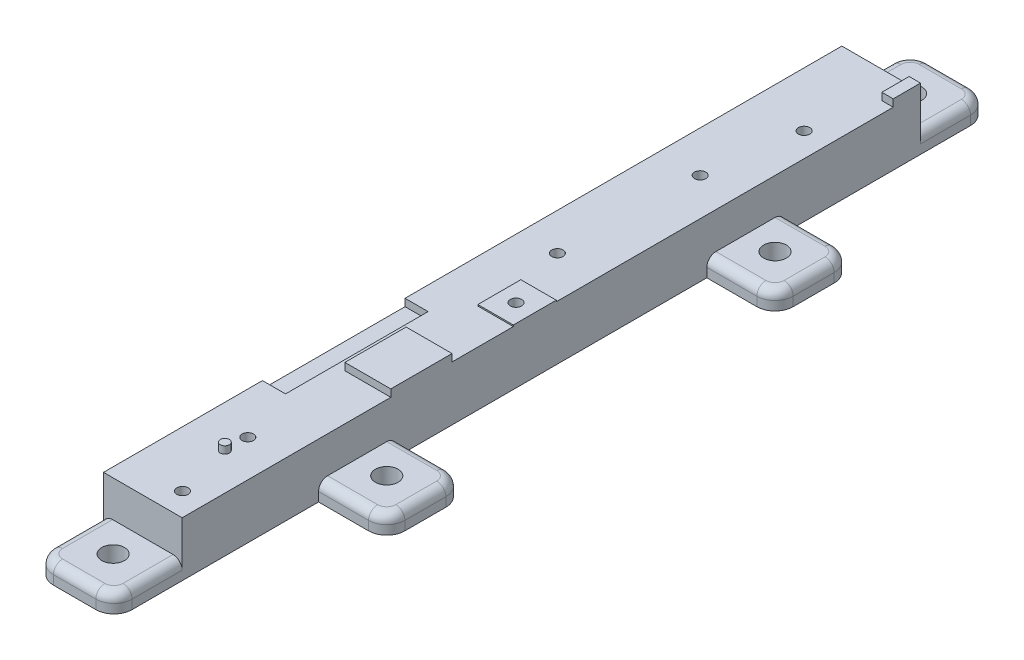
SolidWorks part; units mm, degrees
ref_plane "Front Plane" through (0, 0, 0) normal (0, 0, 1) x (1, 0, 0)
ref_plane "Top Plane" through (0, 0, 0) normal (0, 1, 0) x (1, 0, 0)
ref_plane "Right Plane" through (0, 0, 0) normal (1, 0, 0) x (0, 0, -1)
sketch "Sketch1" plane through (0, 0, 0) normal (0, 1, 0) x (1, 0, 0)
  line L1 (0, 0) -> (-17.3, 0)
  line L2 (0, 0) -> (0, -162.4)
  line L3 (0, -162.4) -> (-17.3, -162.4)
  line L4 (-17.3, 0) -> (-17.3, -162.4)
  line L5 (0, -116.51) -> (-10.1, -116.51)
  line L6 (0, -116.51) -> (0, -103.04)
  line L7 (0, -103.04) -> (-10.1, -103.04)
  line L8 (-10.1, -116.51) -> (-10.1, -103.04)
  line L9 (0, 0) -> (-2.5, 0)
  line L10 (0, 0) -> (0, -6)
  line L11 (0, -6) -> (-2.5, -6)
  line L12 (-2.5, 0) -> (-2.5, -6)
  line L13 (-17.3, -127.44) -> (-12.22, -127.44)
  line L14 (-17.3, -127.44) -> (-17.3, -96.08)
  line L15 (-17.3, -96.08) -> (-12.22, -96.08)
  line L16 (-12.22, -127.44) -> (-12.22, -96.08)
  circle A0 centre (-5.05, -157.28) radius 1.25
  circle A1 centre (-8.115, -144.895) radius 1
  circle A2 centre (-8.115, -139.85) radius 1.25
  circle A3 centre (-3.95, -85.02) radius 1.25
  circle A4 centre (-9.115, -70.745) radius 1.25
  circle A5 centre (-8.25, -40.21) radius 1.25
  circle A6 centre (-5.3, -20.3) radius 1.25
  dimension "D3" = 2.5
  dimension "D6" = 2
  dimension "D9" = 2.5
  dimension "D14" = 2.5
  dimension "D17" = 2.5
  dimension "D20" = 2.5
  dimension "D23" = 2.5
  dimension "D1" = 162.4
  dimension "D2" = 17.3
  dimension "D4" = 5.05
  dimension "D5" = 5.12
  dimension "D7" = 17.505
  dimension "D8" = 8.115
  dimension "D10" = 5.045
  dimension "D11" = 10.1
  dimension "D12" = 13.47
  dimension "D13" = 45.89
  dimension "D15" = 3.95
  dimension "D16" = 77.38
  dimension "D18" = 9.115
  dimension "D19" = 91.655
  dimension "D21" = 8.25
  dimension "D22" = 122.19
  dimension "D24" = 5.3
  dimension "D25" = 142.1
  dimension "D26" = 2.5
  dimension "D27" = 6
  dimension "D28" = 34.96
  dimension "D29" = 66.32
  dimension "D30" = 12.22
extrude "Boss-Extrude1" add sketch "Sketch1" against normal blind 12 contours L16 L13 L4 L3 L2 L5 L8 L7 L11 L12 L1 L15 A6 A5 A4 A3 A2 A1 A0 | L8 L5 L2 L7 | L1 L12 L11 L2 | L13 L16 L15 L4 | A1 region at (-1.25, 0, 3) region at (-8.5237, 0, 77.9924) region at (-5.05, 0, 109.775) region at (-14.76, 0, 111.76) region at (-8.115, 0, 144.895)
extrude "Boss-Extrude2" add sketch "Sketch1<3>" along normal blind 1.6 contours L8 L5 L2 L7 | L1 L12 L11 L2 | A1 region at (-1.25, 0, 3) region at (-5.05, 0, 109.775) region at (-8.115, 0, 144.895)
sketch "Sketch1<3>" plane through (0, 0, 0) normal (0, 1, 0) x (1, 0, 0) same geometry as "Sketch1"
extrude "Cut-Extrude1" cut sketch "Sketch1<4>" against normal blind 1.6 contours L13 L16 L15 L4 region at (-14.76, 0, 111.76)
sketch "Sketch1<4>" plane through (0, 0, 0) normal (0, 1, 0) x (1, 0, 0) same geometry as "Sketch1"
sketch "Sketch2" plane through (0, 0, 0) normal (0, 1, 0) x (1, 0, 0)
  line L0 (0, -6) -> (0, -103.04) construction
  line L1 (0, -80.11) -> (-7.8, -80.11)
  line L2 (0, -80.11) -> (0, -89.56)
  line L3 (0, -89.56) -> (-7.8, -89.56)
  line L4 (-7.8, -80.11) -> (-7.8, -89.56)
  line L5 (0, -162.4) -> (-17.3, -162.4) construction
  line M11 (0, -103.04) -> (0, -6)
  circle M22 centre (-3.95, -85.02) radius 1.25
  dimension "D1" = 72.84
  dimension "D2" = 7.8
  dimension "D3" = 9.45
extrude "Boss-Extrude3" add sketch "Sketch2" along normal blind 0.3 contours L1 L4 L3 M11 M22 region at (-0.1225, 0, 84.835)
sketch "Sketch3" plane through (0, 0, 162.4) normal (0, 0, 1) x (1, 0, 0)
  line L0 (-17.3, -12) -> (-17.3, 0) construction
  line L1 (0, -12) -> (-17.3, -12)
  line L2 (0, -12) -> (0, -8)
  line L3 (0, -8) -> (-17.3, -8)
  line L4 (-17.3, -12) -> (-17.3, -8)
  dimension "D1" = 4
extrude "Boss-Extrude4" add sketch "Sketch3" along normal blind 15
sketch "Sketch4" plane through (0, 0, 0) normal (0, 0, -1) x (-1, 0, 0)
  line L0 (0, -12) -> (0, 1.6) construction
  line L1 (17.3, -12) -> (0, -12)
  line L2 (17.3, -12) -> (17.3, -8)
  line L3 (17.3, -8) -> (0, -8)
  line L4 (0, -12) -> (0, -8)
  dimension "D1" = 4
extrude "Boss-Extrude5" add sketch "Sketch4" along normal blind 15
sketch "Sketch5" plane through (0, 0, 0) normal (1, 0, 0) x (0, 0, -1)
  line L0 (15, -12) -> (-177.4, -12) construction
  line L1 (-132.4, -12) -> (-115.4, -12)
  line L2 (-132.4, -12) -> (-132.4, -8)
  line L3 (-132.4, -8) -> (-115.4, -8)
  line L4 (-115.4, -12) -> (-115.4, -8)
  line L5 (-177.4, -12) -> (-177.4, -8) construction
  line L6 (-47, -12) -> (-30, -12)
  line L7 (-47, -12) -> (-47, -8)
  line L8 (-47, -8) -> (-30, -8)
  line L9 (-30, -12) -> (-30, -8)
  line L10 (15, -8) -> (15, -12) construction
  dimension "D1" = 4
  dimension "D2" = 45
  dimension "D3" = 17
  dimension "D4" = 17
  dimension "D5" = 45
extrude "Boss-Extrude6" add sketch "Sketch5" along normal blind 15
fillet "Fillet1" radius 4 8 edges at (-17.3, -10, -15) (0, -10, -15) (15, -10, 30) (15, -10, 47) (15, -10, 115.4) (15, -10, 132.4) (-17.3, -10, 177.4) (0, -10, 177.4)
fillet "Fillet2" radius 2 20 edges at (-17.3, -8, 167.9) (-16.1284, -8, 176.2284) (-8.65, -8, 177.4) (-1.1716, -8, 176.2284) (5.5, -8, 132.4) (13.8284, -8, 131.2284) (15, -8, 123.9) (13.8284, -8, 116.5716) (5.5, -8, 47) (13.8284, -8, 45.8284) (15, -8, 38.5) (13.8284, -8, 31.1716) (0, -8, -5.5) (-17.3, -8, -5.5) (-16.1284, -8, -13.8284) (-8.65, -8, -15) (0, -8, 167.9) (5.5, -8, 115.4) (5.5, -8, 30) (-1.1716, -8, -13.8284)
sketch "Sketch6" plane through (0, -8, 0) normal (0, 1, 0) x (1, 0, 0)
  line L0 (-15.3, 0) -> (-2, 0) construction
  line L2 (0, -32) -> (0, -45) construction
  line L3 (0, -117.4) -> (0, -130.4) construction
  line L4 (-2, -162.4) -> (-15.3, -162.4) construction
  line L5 (-2, -173.4) -> (-2, -162.4) construction
  line L6 (11, -117.4) -> (0, -117.4) construction
  line L7 (11, -32) -> (0, -32) construction
  circle A0 centre (-8.68, 6.5) radius 2.5
  circle A1 centre (6.5, -38.5) radius 2.5
  circle A2 centre (6.5, -123.9) radius 2.5
  circle A3 centre (-8.68, -168.9) radius 2.5
  point P8 (0, 0)
  dimension "D1" = 5
  dimension "D2" = 6.5
  dimension "D3" = 6.5
  dimension "D4" = 6.5
  dimension "D5" = 6.5
  dimension "D6" = 6.68
  dimension "D7" = 6.5
  dimension "D8" = 6.5
extrude "Cut-Extrude2" cut sketch "Sketch6" against normal up to next
